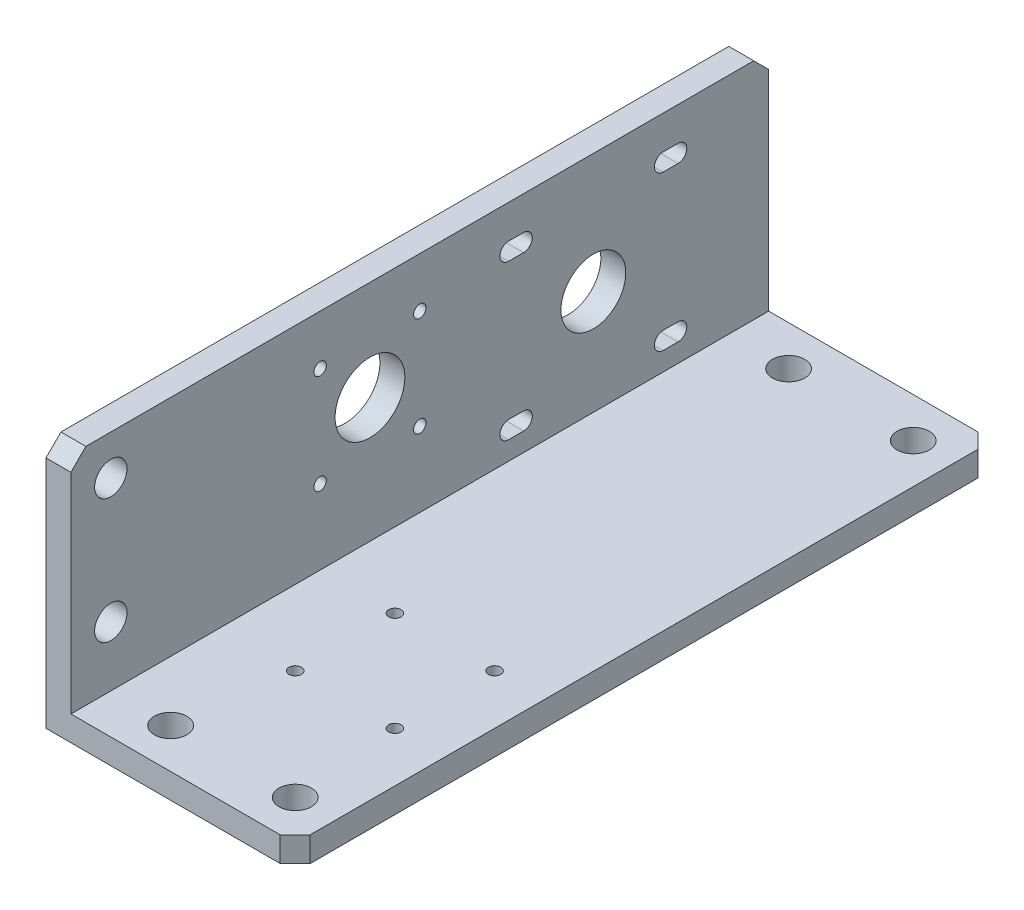
SolidWorks part; units mm, degrees
material "Lega 1060"
ref_plane "Piano frontale" through (0, 0, 0) normal (0, 0, 1) x (1, 0, 0)
ref_plane "Piano superiore" through (0, 0, 0) normal (0, 1, 0) x (1, 0, 0)
ref_plane "Piano destro" through (0, 0, 0) normal (1, 0, 0) x (0, 0, -1)
sketch "Schizzo1" plane through (0, 0, 0) normal (0, 0, 1) x (1, 0, 0)
  line L0 (0, 0) -> (0, 50)
  line L1 (0, 50) -> (5, 50)
  line L2 (5, 50) -> (5, 5)
  line L3 (5, 5) -> (50, 5)
  line L4 (50, 5) -> (50, 0)
  line L5 (50, 0) -> (0, 0)
  dimension "D1" = 5
  dimension "D2" = 5
  dimension "D3" = 50
  dimension "D4" = 50
extrude "Estrusione-Estrusione1" add sketch "Schizzo1" along normal blind 140
sketch "Schizzo2" plane through (0, 0, 0) normal (0, -1, 0) x (1, 0, 0)
  line L0 (5.4524, 132) -> (42.7933, 132) construction
  line L1 (0, 140) -> (50, 140) construction
  line L5 (50, 140) -> (50, 0) construction
  point P4 (17, 132)
  point P5 (42, 132)
  dimension "D1" = 8
  dimension "D2" = 25
  dimension "D3" = 8
sketch "Schizzo3" plane through (0, 0, 0) normal (-1, 0, 0) x (0, 0, 1)
  line L0 (132, 44.621) -> (132, 5.772) construction
  line L1 (140, 50) -> (140, 0) construction
  line L2 (140, 50) -> (0, 50) construction
  point P4 (132, 42)
  point P5 (132, 17)
  dimension "D1" = 8
  dimension "D2" = 8
  dimension "D3" = 25
hole_wizard "Foro Ø6.5 (6.5)-1" positions "Schizzo5" profile "Schizzo4" hole size "Ø6.5" standard "ISO" end condition through all
sketch "Schizzo5" plane through (0, 0, 0) normal (0, -1, 0) x (-1, 0, 0)
  point P0 (-17, -132)
  point P3 (-42, -132)
sketch "Schizzo4" plane through (17, 0, 132) normal (1, 0, 0) x (0, 0, -1)
  line L0 (0, 0) -> (0, 50)
  line L1 (0, 50) -> (3.25, 50)
  line L2 (3.25, 50) -> (3.25, 0)
  line L5 (3.25, 0) -> (0, 0)
  line L11 (0, -6.35) -> (0, 107.95) construction
  dimension "Thru Hole Dia." = 6.5
  dimension "Thru Hole Depth" = 50
hole_wizard "Foro Ø6.5 (6.5)-2" positions "Schizzo7" profile "Schizzo6" hole size "Ø6.5" standard "ISO"
sketch "Schizzo7" plane through (0, 0, 0) normal (-1, 0, 0) x (0, 0, 1)
  point P1 (132, 42)
  point P4 (132, 17)
sketch "Schizzo6" plane through (0, 42, 132) normal (0, 1, 0) x (0, 0, 1)
  line L0 (0, 0) -> (0, 6.9528)
  line L1 (0, 6.9528) -> (3.25, 5)
  line L2 (3.25, 5) -> (3.25, 0)
  line L5 (3.25, 0) -> (0, 0)
  line L10 (0, 6.9528) -> (-3.25, 5) construction
  line L11 (0, -6.35) -> (0, 107.95) construction
  dimension "Hole Dia." = 6.5
  dimension "Hole Depth" = 5
  dimension "Drill Angle" = 118
ref_plane "Piano1" through (0, 0, 70) normal (0, 0, 1) x (1, 0, 0)
mirror "Specchia1" about plane through (0, 0, 70) normal (0, 0, 1) of "Foro Ø6.5 (6.5)-1"
sketch "Schizzo10" plane through (0, 0, 0) normal (-1, 0, 0) x (0, 0, 1)
  line L3 (140, 50) -> (140, 0) construction
  line L5 (140, 50) -> (0, 50) construction
  circle A5 centre (80, 30) radius 7
  point P8 (80, 30)
  point P20 (80, 30)
  dimension "D7" = 14
  dimension "D5" = 60
  dimension "D6" = 20
extrude "Taglio-Estrusione3" cut sketch "Schizzo10" against normal up to next
sketch "Schizzo11" plane through (0, 0, 0) normal (0, -1, 0) x (1, 0, 0)
  line L0 (30, 100) -> (14.4837, 100) construction
  line L1 (30, 100) -> (4.5929, 74.5929) construction
  line L3 (50, 140) -> (50, 0) construction
  line L4 (0, 140) -> (50, 140) construction
  circle A0 centre (20, 90) radius 1.75
  circle A3 centre (20, 110) radius 1.75
  circle A4 centre (40, 110) radius 1.75
  circle A5 centre (40, 90) radius 1.75
  point P2 (30, 100)
  point P17 (30, 100)
  dimension "D2" = 3.5
  dimension "D1" = 20
  dimension "D3" = 45
  dimension "D5" = 20
  dimension "D6" = 40
  dimension "D4" = 4
sketch "Schizzo13" plane through (0, 0, 0) normal (-1, 0, 0) x (0, 0, 1)
  line L0 (68.5583, 26) -> (16.2744, 26) construction
  line L2 (140, 0) -> (0, 0) construction
  line L3 (18.1781, 41.5) -> (21.1781, 41.5) construction
  line L4 (18.1781, 43.25) -> (21.1781, 43.25)
  line L5 (18.1781, 39.75) -> (21.1781, 39.75)
  line L6 (18.1781, 10.5) -> (21.1781, 10.5) construction
  line L7 (18.1781, 8.75) -> (21.1781, 8.75)
  line L8 (18.1781, 12.25) -> (21.1781, 12.25)
  line L9 (35.1781, 26) -> (35.1781, 7.2619) construction
  line L10 (52.1781, 41.5) -> (49.1781, 41.5) construction
  line L11 (52.1781, 43.25) -> (49.1781, 43.25)
  line L12 (52.1781, 39.75) -> (49.1781, 39.75)
  line L13 (52.1781, 10.5) -> (49.1781, 10.5) construction
  line L14 (52.1781, 8.75) -> (49.1781, 8.75)
  line L15 (52.1781, 12.25) -> (49.1781, 12.25)
  arc A0 (52.1781, 43.25) -> (52.1781, 39.75) centre (52.1781, 41.5) cw
  arc A2 (18.1781, 43.25) -> (18.1781, 39.75) centre (18.1781, 41.5) ccw
  arc A3 (49.1781, 39.75) -> (49.1781, 43.25) centre (49.1781, 41.5) cw
  arc A4 (18.1781, 8.75) -> (18.1781, 12.25) centre (18.1781, 10.5) cw
  arc A5 (21.1781, 12.25) -> (21.1781, 8.75) centre (21.1781, 10.5) cw
  circle A6 centre (35.1781, 26) radius 6.5
  arc A7 (21.1781, 39.75) -> (21.1781, 43.25) centre (21.1781, 41.5) ccw
  circle A8 centre (80, 30) radius 7 construction
  arc A10 (52.1781, 8.75) -> (52.1781, 12.25) centre (52.1781, 10.5) ccw
  arc A11 (49.1781, 12.25) -> (49.1781, 8.75) centre (49.1781, 10.5) ccw
  point P8 (35.1781, 26)
  point P13 (50.6781, 41.5)
  point P17 (19.6781, 10.5)
  point P19 (35.1781, 26)
  point P22 (19.6781, 41.5)
  point P40 (50.6781, 10.5)
  dimension "D2" = 13
  dimension "D4" = 45
  dimension "D1" = 31
  dimension "D3" = 31
  dimension "D5" = 26
  dimension "D8" = 3.5
  dimension "D9" = 3
extrude "Taglio-Estrusione6" cut sketch "Schizzo13" against normal up to next
chamfer "Smusso1" distance 3 angle 45 4 edges at (50, 2.5, 0) (2.5, 50, 0) (50, 2.5, 140) (2.5, 50, 140)
sketch "Sketch1" plane through (0, 0, 0) normal (-1, 0, 0) x (0, 0, 1)
  line L0 (80, 30) -> (80, 46.7736) construction
  line L1 (80, 46.7736) -> (80, 30) construction
  line L2 (80, 30) -> (63.2264, 46.7736) construction
  line L3 (63.2264, 46.7736) -> (80, 30) construction
  line L4 (80, 30) -> (62.4784, 30) construction
  point P3 (70, 40)
  point P6 (90, 40)
  point P7 (70, 20)
  point P8 (90, 20)
  dimension "D1" = 45
  dimension "D2" = 10
hole_wizard "M3 Tapped Hole1" positions "3DSketch1" profile "Sketch2" tap size "M3" standard "ISO" end condition through all
sketch3d "3DSketch1"
  point P0 (0, 40, 70)
  point P3 (0, 40, 90)
  point P6 (0, 20, 90)
  point P9 (0, 20, 70)
sketch "Sketch2" plane through (0, 40, 70) normal (0, 1, 0) x (0, 0, 1)
  line L0 (0, 0) -> (0, 50)
  line L1 (0, 50) -> (1.25, 50)
  line L2 (1.25, 50) -> (1.25, 0)
  line L5 (1.25, 0) -> (0, 0)
  line L11 (0, -6.35) -> (0, 107.95) construction
  dimension "Thru Tap Drill Dia." = 2.5
  dimension "Thru Tap Drill Depth" = 50
cosmetic thread "Cosmetic Thread1" parameters "D2"=3
cosmetic thread "Cosmetic Thread2" parameters "D2"=3
cosmetic thread "Cosmetic Thread3" parameters "D2"=3
cosmetic thread "Cosmetic Thread4" parameters "D2"=3
hole_wizard "M3 Tapped Hole2" positions "3DSketch2" profile "Sketch3" tap size "M3" standard "ISO" end condition through all
sketch3d "3DSketch2"
  point P0 (20, 0, 110)
  point P3 (40, 0, 110)
  point P6 (40, 0, 90)
  point P9 (20, 0, 90)
sketch "Sketch3" plane through (20, 0, 110) normal (1, 0, 0) x (0, 0, -1)
  line L0 (0, 0) -> (0, 50)
  line L1 (0, 50) -> (1.25, 50)
  line L2 (1.25, 50) -> (1.25, 0)
  line L5 (1.25, 0) -> (0, 0)
  line L11 (0, -6.35) -> (0, 107.95) construction
  dimension "Thru Tap Drill Dia." = 2.5
  dimension "Thru Tap Drill Depth" = 50
cosmetic thread "Cosmetic Thread5" parameters "D2"=3
cosmetic thread "Cosmetic Thread6" parameters "D2"=3
cosmetic thread "Cosmetic Thread7" parameters "D2"=3
cosmetic thread "Cosmetic Thread8" parameters "D2"=3
